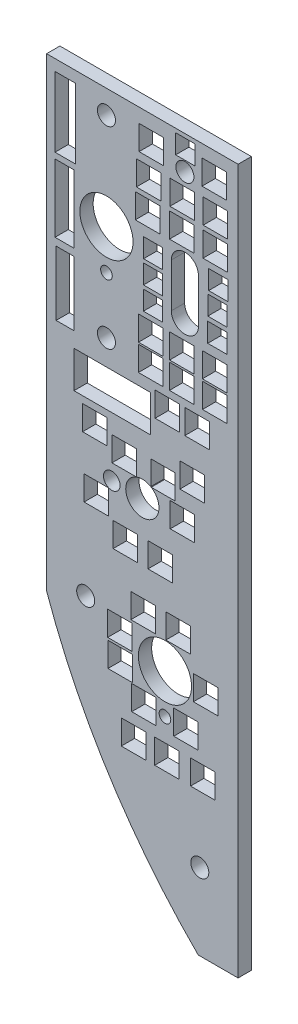
SolidWorks part; units mm, degrees
material "Acrylic (Medium-high impact)"
ref_plane "Front Plane" through (0, 0, 0) normal (0, 0, 1) x (1, 0, 0)
ref_plane "Top Plane" through (0, 0, 0) normal (0, 1, 0) x (1, 0, 0)
ref_plane "Right Plane" through (0, 0, 0) normal (1, 0, 0) x (0, 0, -1)
sketch "Sketch1" plane through (0, 0, 0) normal (0, 0, 1) x (1, 0, 0)
  line L4 (-45.72, 26.9875) -> (-45.72, -84.1375)
  line L5 (-9.525, -141.2875) -> (0, -141.2875)
  line L6 (0, -141.2875) -> (0, 26.9875)
  line L7 (0, 26.9875) -> (-45.72, 26.9875)
  line L8 (-45.72, 26.9875) -> (-45.72, -84.1375)
  line L9 (-9.525, -141.2875) -> (0, -141.2875)
  line L10 (0, -141.2875) -> (0, 26.9875)
  line L11 (0, 26.9875) -> (-45.72, 26.9875)
  arc A1 (-45.72, -84.1375) -> (-9.525, -141.2875) centre (97.9169, -33.2042) ccw
  arc A2 (-45.72, -84.1375) -> (-9.525, -141.2875) centre (97.9169, -33.2042) ccw
  dimension "D1" = 0
extrude "Boss-Extrude1" add sketch "Sketch1" against normal blind 3.175
hole_wizard "1/2 (0.5) Diameter Hole1" positions "Sketch4" profile "Sketch3" hole size "1/2" standard "ANSI Inch" end condition through all
sketch "Sketch4" plane through (0, 0, 0) normal (0, 0, 1) x (1, 0, 0)
  point P0 (-17.4625, -86.5505)
  point P4 (-31.4325, -1.6203)
sketch "Sketch3" plane through (-17.4625, -86.5505, 0) normal (1, 0, 0) x (0, -1, 0)
  line L0 (0, 0) -> (0, 3.175)
  line L1 (0, 3.175) -> (6.35, 3.175)
  line L2 (6.35, 3.175) -> (6.35, 0)
  line L5 (6.35, 0) -> (0, 0)
  line L11 (0, -6.35) -> (0, 107.95) construction
  dimension "Thru Hole Dia." = 12.7
  dimension "Thru Hole Depth" = 3.175
hole_wizard "5/16 (0.3125) Diameter Hole1" positions "Sketch6" profile "Sketch5" hole size "5/16" standard "ANSI Inch" end condition through all
sketch "Sketch6" plane through (0, 0, 0) normal (0, 0, 1) x (1, 0, 0)
  point P0 (-22.86, -53.5305)
sketch "Sketch5" plane through (-22.86, -53.5305, 0) normal (1, 0, 0) x (0, -1, 0)
  line L0 (0, 0) -> (0, 3.175)
  line L1 (0, 3.175) -> (3.9687, 3.175)
  line L2 (3.9687, 3.175) -> (3.9687, 0)
  line L5 (3.9687, 0) -> (0, 0)
  line L11 (0, -6.35) -> (0, 107.95) construction
  dimension "Thru Hole Dia." = 7.9375
  dimension "Thru Hole Depth" = 3.175
hole_wizard "5/32 (0.15625) Diameter Hole1" positions "Sketch8" profile "Sketch7" hole size "5/32" standard "ANSI Inch" end condition through all
sketch "Sketch8" plane through (0, 0, 0) normal (0, 0, 1) x (1, 0, 0)
  line L0 (-22.86, -49.5617) -> (-22.86, -53.5305) construction
  circle A0 centre (-22.86, -53.5305) radius 3.9688 construction
  point P11 (-30.1611, -53.5305)
sketch "Sketch7" plane through (-30.1611, -53.5305, 0) normal (1, 0, 0) x (0, -1, 0)
  line L0 (0, 0) -> (0, 3.175)
  line L1 (0, 3.175) -> (1.9844, 3.175)
  line L2 (1.9844, 3.175) -> (1.9844, 0)
  line L5 (1.9844, 0) -> (0, 0)
  line L11 (0, -6.35) -> (0, 107.95) construction
  dimension "Thru Hole Dia." = 3.9688
  dimension "Thru Hole Depth" = 3.175
hole_wizard "7/64 (0.10938) Diameter Hole1" positions "Sketch10" profile "Sketch9" hole size "7/64" standard "ANSI Inch" end condition through all
sketch "Sketch10" plane through (0, 0, 0) normal (0, 0, 1) x (1, 0, 0)
  point P0 (-17.4646, -95.9667)
  point P3 (-31.4325, -11.1589)
sketch "Sketch9" plane through (-17.4646, -95.9667, 0) normal (1, 0, 0) x (0, -1, 0)
  line L0 (0, 0) -> (0, 3.175)
  line L1 (0, 3.175) -> (1.3891, 3.175)
  line L2 (1.3891, 3.175) -> (1.3891, 0)
  line L5 (1.3891, 0) -> (0, 0)
  line L11 (0, -6.35) -> (0, 107.95) construction
  dimension "Thru Hole Dia." = 2.7783
  dimension "Thru Hole Depth" = 3.175
sketch "Sketch11" plane through (0, 0, -3.175) normal (0, 0, -1) x (-1, 0, 0)
  line L5 (19.8437, -15.24) -> (19.8437, 3.175)
  line L6 (19.8437, 3.175) -> (8.7312, 3.175)
  line L7 (8.7312, 3.175) -> (8.7312, -15.24)
  line L8 (8.7312, -15.24) -> (19.8437, -15.24)
  line L9 (19.8437, -15.24) -> (19.8437, 3.175)
  line L10 (19.8437, 3.175) -> (8.7312, 3.175)
  line L11 (8.7312, 3.175) -> (8.7312, -15.24)
  line L12 (8.7312, -15.24) -> (19.8437, -15.24)
  dimension "D1" = 0
extrude "Cut-Extrude4" [suppressed] cut sketch "Sketch11" against normal through all
hole_wizard "#6 Clearance Hole1" positions "Sketch13" profile "Sketch12" hole size "#6" standard "ANSI Inch" end condition through all
sketch "Sketch13" plane through (0, 0, -3.175) normal (0, 0, -1) x (-1, 0, 0)
  point P0 (12.7, 19.05)
  point P3 (36.3855, -80.4545)
  point P6 (9.144, -122.9995)
  point P10 (31.4325, -24.62)
  point P13 (31.4325, 21.4048)
sketch "Sketch12" plane through (-12.7, 19.05, -3.175) normal (1, 0, 0) x (0, 1, 0)
  line L0 (0, 0) -> (0, 3.175)
  line L1 (0, 3.175) -> (2.1526, 3.175)
  line L2 (2.1526, 3.175) -> (2.1526, 0)
  line L5 (2.1526, 0) -> (0, 0)
  line L11 (0, -6.35) -> (0, 107.95) construction
  dimension "Thru Hole Dia." = 4.3053
  dimension "Thru Hole Depth" = 3.175
hole_wizard "#16 (0.177) Diameter Hole1" positions "Sketch15" profile "Sketch14" hole size "#16" standard "ANSI Inch" end condition through all
sketch "Sketch15" plane through (0, 0, -3.175) normal (0, 0, -1) x (-1, 0, 0)
  line L5 (12.7, 2.794) -> (12.7, -14.859) construction
  line L6 (12.7, -6.0325) -> (17.8753, -6.0325) construction
  point P26 (12.7, -0.7804)
  point P33 (12.7, -11.2846)
sketch "Sketch14" plane through (-12.7, -11.2846, -3.175) normal (1, 0, 0) x (0, 1, 0)
  line L0 (0, 0) -> (0, 3.175)
  line L1 (0, 3.175) -> (2.2479, 3.175)
  line L2 (2.2479, 3.175) -> (2.2479, 0)
  line L5 (2.2479, 0) -> (0, 0)
  line L11 (0, -6.35) -> (0, 107.95) construction
  dimension "Thru Hole Dia." = 4.4958
  dimension "Thru Hole Depth" = 3.175
sketch "Sketch16" plane through (0, 0, -4.775) normal (0, 0, -1) x (-1, 0, 0)
  line L0 (12.7, -11.2846) -> (12.7, -0.7804) construction
  line L1 (2.6659, -22.1354) -> (8.5079, -22.1354)
  line L2 (2.6659, -22.1354) -> (2.6659, -27.9774)
  line L3 (2.6659, -27.9774) -> (8.5079, -27.9774)
  line L4 (8.5079, -22.1354) -> (8.5079, -27.9774)
  line L5 (2.6659, -22.1354) -> (8.5079, -27.9774) construction
  line L6 (2.6659, -27.9774) -> (8.5079, -22.1354) construction
  line L7 (10.5519, -22.1354) -> (16.3939, -22.1354)
  line L8 (10.5519, -22.1354) -> (10.5519, -27.9774)
  line L9 (10.5519, -27.9774) -> (16.3939, -27.9774)
  line L10 (16.3939, -22.1354) -> (16.3939, -27.9774)
  line L11 (10.5519, -22.1354) -> (16.3939, -27.9774) construction
  line L12 (10.5519, -27.9774) -> (16.3939, -22.1354) construction
  line L13 (17.9569, -22.1354) -> (23.7989, -22.1354)
  line L14 (17.9569, -22.1354) -> (17.9569, -27.9774)
  line L15 (17.9569, -27.9774) -> (23.7989, -27.9774)
  line L16 (23.7989, -22.1354) -> (23.7989, -27.9774)
  line L17 (17.9569, -22.1354) -> (23.7989, -27.9774) construction
  line L18 (17.9569, -27.9774) -> (23.7989, -22.1354) construction
  line L19 (17.9319, -15.8614) -> (23.7739, -15.8614)
  line L20 (17.9319, -15.8614) -> (17.9319, -21.7034)
  line L21 (17.9319, -21.7034) -> (23.7739, -21.7034)
  line L22 (23.7739, -15.8614) -> (23.7739, -21.7034)
  line L23 (17.9319, -15.8614) -> (23.7739, -21.7034) construction
  line L24 (17.9319, -21.7034) -> (23.7739, -15.8614) construction
  line L25 (10.5149, -15.8364) -> (16.3569, -15.8364)
  line L26 (10.5149, -15.8364) -> (10.5149, -21.6784)
  line L27 (10.5149, -21.6784) -> (16.3569, -21.6784)
  line L28 (16.3569, -15.8364) -> (16.3569, -21.6784)
  line L29 (10.5149, -15.8364) -> (16.3569, -21.6784) construction
  line L30 (10.5149, -21.6784) -> (16.3569, -15.8364) construction
  line L31 (2.6919, -15.8114) -> (8.5339, -15.8114)
  line L32 (2.6919, -15.8114) -> (2.6919, -21.6534)
  line L33 (2.6919, -21.6534) -> (8.5339, -21.6534)
  line L34 (8.5339, -15.8114) -> (8.5339, -21.6534)
  line L35 (2.6919, -15.8114) -> (8.5339, -21.6534) construction
  line L36 (2.6919, -21.6534) -> (8.5339, -15.8114) construction
  line L41 (39.2165, -27.0307) -> (43.4505, -27.0307)
  line L42 (39.2165, -27.0307) -> (39.2165, -11.6644)
  line L47 (39.2165, -11.6644) -> (43.4505, -11.6644)
  line L48 (43.4505, -27.0307) -> (43.4505, -11.6644)
  line L53 (39.2165, 6.231) -> (43.7187, 6.231)
  line L54 (39.2165, 6.231) -> (39.2165, -9.9754)
  line L55 (39.2165, -9.9754) -> (43.7187, -9.9754)
  line L56 (43.7187, 6.231) -> (43.7187, -9.9754)
  line L57 (38.8582, 7.6135) -> (43.7187, 7.6135)
  line L58 (38.8582, 7.6135) -> (38.8582, 24.3196)
  line L59 (38.8582, 24.3196) -> (43.7187, 24.3196)
  line L60 (43.7187, 7.6135) -> (43.7187, 24.3196)
  line L61 (12.7249, -29.6544) -> (6.8829, -29.6544)
  line L62 (12.7249, -29.6544) -> (12.7249, -35.4964)
  line L63 (12.7249, -35.4964) -> (6.8829, -35.4964)
  line L64 (6.8829, -29.6544) -> (6.8829, -35.4964)
  line L65 (12.7249, -29.6544) -> (6.8829, -35.4964) construction
  line L66 (12.7249, -35.4964) -> (6.8829, -29.6544) construction
  line L67 (19.8109, -29.6034) -> (13.9689, -29.6034)
  line L68 (19.8109, -29.6034) -> (19.8109, -35.4454)
  line L69 (19.8109, -35.4454) -> (13.9689, -35.4454)
  line L70 (13.9689, -29.6034) -> (13.9689, -35.4454)
  line L71 (19.8109, -29.6034) -> (13.9689, -35.4454) construction
  line L72 (19.8109, -35.4454) -> (13.9689, -29.6034) construction
  line L73 (5.5089, -101.4346) -> (11.3509, -101.4346)
  line L74 (5.5089, -101.4346) -> (5.5089, -107.2766)
  line L75 (5.5089, -107.2766) -> (11.3509, -107.2766)
  line L76 (11.3509, -101.4346) -> (11.3509, -107.2766)
  line L77 (5.5089, -101.4346) -> (11.3509, -107.2766) construction
  line L78 (5.5089, -107.2766) -> (11.3509, -101.4346) construction
  line L79 (14.0689, -101.4088) -> (19.9109, -101.4088)
  line L80 (14.0689, -101.4088) -> (14.0689, -107.2508)
  line L81 (14.0689, -107.2508) -> (19.9109, -107.2508)
  line L82 (19.9109, -101.4088) -> (19.9109, -107.2508)
  line L83 (14.0689, -101.4088) -> (19.9109, -107.2508) construction
  line L84 (14.0689, -107.2508) -> (19.9109, -101.4088) construction
  line L85 (22.0469, -101.4342) -> (27.8889, -101.4342)
  line L86 (22.0469, -101.4342) -> (22.0469, -107.2762)
  line L87 (22.0469, -107.2762) -> (27.8889, -107.2762)
  line L88 (27.8889, -101.4342) -> (27.8889, -107.2762)
  line L89 (22.0469, -101.4342) -> (27.8889, -107.2762) construction
  line L90 (22.0469, -107.2762) -> (27.8889, -101.4342) construction
  line L91 (9.5239, -93.1288) -> (15.3659, -93.1288)
  line L92 (9.5239, -93.1288) -> (9.5239, -98.9708)
  line L93 (9.5239, -98.9708) -> (15.3659, -98.9708)
  line L94 (15.3659, -93.1288) -> (15.3659, -98.9708)
  line L95 (9.5239, -93.1288) -> (15.3659, -98.9708) construction
  line L96 (9.5239, -98.9708) -> (15.3659, -93.1288) construction
  line L97 (19.5569, -93.0776) -> (25.3989, -93.0776)
  line L98 (19.5569, -93.0776) -> (19.5569, -98.9196)
  line L99 (19.5569, -98.9196) -> (25.3989, -98.9196)
  line L100 (25.3989, -93.0776) -> (25.3989, -98.9196)
  line L101 (19.5569, -93.0776) -> (25.3989, -98.9196) construction
  line L102 (19.5569, -98.9196) -> (25.3989, -93.0776) construction
  line L103 (4.8249, -83.6546) -> (10.6669, -83.6546)
  line L104 (4.8249, -83.6546) -> (4.8249, -89.4966)
  line L105 (4.8249, -89.4966) -> (10.6669, -89.4966)
  line L106 (10.6669, -83.6546) -> (10.6669, -89.4966)
  line L107 (4.8249, -83.6546) -> (10.6669, -89.4966) construction
  line L108 (4.8249, -89.4966) -> (10.6669, -83.6546) construction
  line L109 (25.2329, -86.9818) -> (31.0749, -86.9818)
  line L110 (25.2329, -86.9818) -> (25.2329, -92.8238)
  line L111 (25.2329, -92.8238) -> (31.0749, -92.8238)
  line L112 (31.0749, -86.9818) -> (31.0749, -92.8238)
  line L113 (25.2329, -86.9818) -> (31.0749, -92.8238) construction
  line L114 (25.2329, -92.8238) -> (31.0749, -86.9818) construction
  line L115 (25.2959, -80.5808) -> (31.1379, -80.5808)
  line L116 (25.2959, -80.5808) -> (25.2959, -86.4228)
  line L117 (25.2959, -86.4228) -> (31.1379, -86.4228)
  line L118 (31.1379, -80.5808) -> (31.1379, -86.4228)
  line L119 (25.2959, -80.5808) -> (31.1379, -86.4228) construction
  line L120 (25.2959, -86.4228) -> (31.1379, -80.5808) construction
  line L121 (19.7609, -74.1546) -> (25.6029, -74.1546)
  line L122 (19.7609, -74.1546) -> (19.7609, -79.9966)
  line L123 (19.7609, -79.9966) -> (25.6029, -79.9966)
  line L124 (25.6029, -74.1546) -> (25.6029, -79.9966)
  line L125 (19.7609, -74.1546) -> (25.6029, -79.9966) construction
  line L126 (19.7609, -79.9966) -> (25.6029, -74.1546) construction
  line L127 (11.4019, -74.1804) -> (17.2439, -74.1804)
  line L128 (11.4019, -74.1804) -> (11.4019, -80.0224)
  line L129 (11.4019, -80.0224) -> (17.2439, -80.0224)
  line L130 (17.2439, -74.1804) -> (17.2439, -80.0224)
  line L131 (11.4019, -74.1804) -> (17.2439, -80.0224) construction
  line L132 (11.4019, -80.0224) -> (17.2439, -74.1804) construction
  line L133 (15.6709, -61.6074) -> (21.5129, -61.6074)
  line L134 (15.6709, -61.6074) -> (15.6709, -67.4494)
  line L135 (15.6709, -67.4494) -> (21.5129, -67.4494)
  line L136 (21.5129, -61.6074) -> (21.5129, -67.4494)
  line L137 (15.6709, -61.6074) -> (21.5129, -67.4494) construction
  line L138 (15.6709, -67.4494) -> (21.5129, -61.6074) construction
  line L139 (24.0019, -61.582) -> (29.8439, -61.582)
  line L140 (24.0019, -61.582) -> (24.0019, -67.424)
  line L141 (24.0019, -67.424) -> (29.8439, -67.424)
  line L142 (29.8439, -61.582) -> (29.8439, -67.424)
  line L143 (24.0019, -61.582) -> (29.8439, -67.424) construction
  line L144 (24.0019, -67.424) -> (29.8439, -61.582) construction
  line L145 (30.9369, -55.4098) -> (36.7789, -55.4098)
  line L146 (30.9369, -55.4098) -> (30.9369, -61.2518)
  line L147 (30.9369, -61.2518) -> (36.7789, -61.2518)
  line L148 (36.7789, -55.4098) -> (36.7789, -61.2518)
  line L149 (30.9369, -55.4098) -> (36.7789, -61.2518) construction
  line L150 (30.9369, -61.2518) -> (36.7789, -55.4098) construction
  line L151 (10.3599, -50.66) -> (16.2019, -50.66)
  line L152 (10.3599, -50.66) -> (10.3599, -56.502)
  line L153 (10.3599, -56.502) -> (16.2019, -56.502)
  line L154 (16.2019, -50.66) -> (16.2019, -56.502)
  line L155 (10.3599, -50.66) -> (16.2019, -56.502) construction
  line L156 (10.3599, -56.502) -> (16.2019, -50.66) construction
  line L157 (8.0509, -41.2874) -> (13.8929, -41.2874)
  line L158 (8.0509, -41.2874) -> (8.0509, -47.1294)
  line L159 (8.0509, -47.1294) -> (13.8929, -47.1294)
  line L160 (13.8929, -41.2874) -> (13.8929, -47.1294)
  line L161 (8.0509, -41.2874) -> (13.8929, -47.1294) construction
  line L162 (8.0509, -47.1294) -> (13.8929, -41.2874) construction
  line L163 (15.0109, -44.3354) -> (20.8529, -44.3354)
  line L164 (15.0109, -44.3354) -> (15.0109, -50.1774)
  line L165 (15.0109, -50.1774) -> (20.8529, -50.1774)
  line L166 (20.8529, -44.3354) -> (20.8529, -50.1774)
  line L167 (15.0109, -44.3354) -> (20.8529, -50.1774) construction
  line L168 (15.0109, -50.1774) -> (20.8529, -44.3354) construction
  line L169 (24.2819, -43.9798) -> (30.1239, -43.9798)
  line L170 (24.2819, -43.9798) -> (24.2819, -49.8218)
  line L171 (24.2819, -49.8218) -> (30.1239, -49.8218)
  line L172 (30.1239, -43.9798) -> (30.1239, -49.8218)
  line L173 (24.2819, -43.9798) -> (30.1239, -49.8218) construction
  line L174 (24.2819, -49.8218) -> (30.1239, -43.9798) construction
  line L175 (31.2919, -41.0588) -> (37.1339, -41.0588)
  line L176 (31.2919, -41.0588) -> (31.2919, -46.9008)
  line L177 (31.2919, -46.9008) -> (37.1339, -46.9008)
  line L178 (37.1339, -41.0588) -> (37.1339, -46.9008)
  line L179 (31.2919, -41.0588) -> (37.1339, -46.9008) construction
  line L180 (31.2919, -46.9008) -> (37.1339, -41.0588) construction
  line L185 (9.4609, -11.2846) -> (9.4609, -0.7804)
  line L186 (15.9391, -11.2846) -> (15.9391, -0.7804)
  line L191 (39.1895, -30.6633) -> (20.8742, -30.6633)
  line L192 (39.1895, -30.6633) -> (39.1895, -39.4353)
  line L193 (2.6809, -9.0944) -> (7.2529, -9.0944)
  line L194 (2.6809, -9.0944) -> (2.6809, -13.6664)
  line L195 (2.6809, -13.6664) -> (7.2529, -13.6664)
  line L196 (7.2529, -9.0944) -> (7.2529, -13.6664)
  line L197 (2.6809, -9.0944) -> (7.2529, -13.6664) construction
  line L198 (2.6809, -13.6664) -> (7.2529, -9.0944) construction
  line L199 (2.6659, -3.4664) -> (7.2379, -3.4664)
  line L200 (2.6659, -3.4664) -> (2.6659, -8.0384)
  line L201 (2.6659, -8.0384) -> (7.2379, -8.0384)
  line L202 (7.2379, -3.4664) -> (7.2379, -8.0384)
  line L203 (2.6659, -3.4664) -> (7.2379, -8.0384) construction
  line L204 (2.6659, -8.0384) -> (7.2379, -3.4664) construction
  line L205 (2.4609, 1.9176) -> (7.0329, 1.9176)
  line L206 (2.4609, 1.9176) -> (2.4609, -2.6544)
  line L207 (2.4609, -2.6544) -> (7.0329, -2.6544)
  line L208 (7.0329, 1.9176) -> (7.0329, -2.6544)
  line L209 (2.4609, 1.9176) -> (7.0329, -2.6544) construction
  line L210 (2.4609, -2.6544) -> (7.0329, 1.9176) construction
  line L211 (2.5389, 9.2076) -> (8.3809, 9.2076)
  line L212 (2.5389, 9.2076) -> (2.5389, 3.3656)
  line L213 (2.5389, 3.3656) -> (8.3809, 3.3656)
  line L214 (8.3809, 9.2076) -> (8.3809, 3.3656)
  line L215 (2.5389, 9.2076) -> (8.3809, 3.3656) construction
  line L216 (2.5389, 3.3656) -> (8.3809, 9.2076) construction
  line L217 (10.5379, 9.1566) -> (16.3799, 9.1566)
  line L218 (10.5379, 9.1566) -> (10.5379, 3.3146)
  line L219 (10.5379, 3.3146) -> (16.3799, 3.3146)
  line L220 (16.3799, 9.1566) -> (16.3799, 3.3146)
  line L221 (10.5379, 9.1566) -> (16.3799, 3.3146) construction
  line L222 (10.5379, 3.3146) -> (16.3799, 9.1566) construction
  line L223 (18.7049, 9.0556) -> (24.5469, 9.0556)
  line L224 (18.7049, 9.0556) -> (18.7049, 3.2136)
  line L225 (18.7049, 3.2136) -> (24.5469, 3.2136)
  line L226 (24.5469, 9.0556) -> (24.5469, 3.2136)
  line L227 (18.7049, 9.0556) -> (24.5469, 3.2136) construction
  line L228 (18.7049, 3.2136) -> (24.5469, 9.0556) construction
  line L229 (17.9969, 0.7356) -> (22.5689, 0.7356)
  line L230 (17.9969, 0.7356) -> (17.9969, -3.8364)
  line L231 (17.9969, -3.8364) -> (22.5689, -3.8364)
  line L232 (22.5689, 0.7356) -> (22.5689, -3.8364)
  line L233 (17.9969, 0.7356) -> (22.5689, -3.8364) construction
  line L234 (17.9969, -3.8364) -> (22.5689, 0.7356) construction
  line L235 (18.0219, -4.6994) -> (22.5939, -4.6994)
  line L236 (18.0219, -4.6994) -> (18.0219, -9.2714)
  line L237 (18.0219, -9.2714) -> (22.5939, -9.2714)
  line L238 (22.5939, -4.6994) -> (22.5939, -9.2714)
  line L239 (18.0219, -4.6994) -> (22.5939, -9.2714) construction
  line L240 (18.0219, -9.2714) -> (22.5939, -4.6994) construction
  line L241 (18.0479, -10.1354) -> (22.6199, -10.1354)
  line L242 (18.0479, -10.1354) -> (18.0479, -14.7074)
  line L243 (18.0479, -14.7074) -> (22.6199, -14.7074)
  line L244 (22.6199, -10.1354) -> (22.6199, -14.7074)
  line L245 (18.0479, -10.1354) -> (22.6199, -14.7074) construction
  line L246 (18.0479, -14.7074) -> (22.6199, -10.1354) construction
  line L247 (2.4859, 16.0666) -> (8.3279, 16.0666)
  line L248 (2.4859, 16.0666) -> (2.4859, 10.2246)
  line L249 (2.4859, 10.2246) -> (8.3279, 10.2246)
  line L250 (8.3279, 16.0666) -> (8.3279, 10.2246)
  line L251 (2.4859, 16.0666) -> (8.3279, 10.2246) construction
  line L252 (2.4859, 10.2246) -> (8.3279, 16.0666) construction
  line L253 (10.4389, 15.9896) -> (16.2809, 15.9896)
  line L254 (10.4389, 15.9896) -> (10.4389, 10.1476)
  line L255 (10.4389, 10.1476) -> (16.2809, 10.1476)
  line L256 (16.2809, 15.9896) -> (16.2809, 10.1476)
  line L257 (10.4389, 15.9896) -> (16.2809, 10.1476) construction
  line L258 (10.4389, 10.1476) -> (16.2809, 15.9896) construction
  line L259 (18.4399, 15.9896) -> (24.2819, 15.9896)
  line L260 (18.4399, 15.9896) -> (18.4399, 10.1476)
  line L261 (18.4399, 10.1476) -> (24.2819, 10.1476)
  line L262 (24.2819, 15.9896) -> (24.2819, 10.1476)
  line L263 (18.4399, 15.9896) -> (24.2819, 10.1476) construction
  line L264 (18.4399, 10.1476) -> (24.2819, 15.9896) construction
  line L265 (17.8049, 23.6096) -> (23.6469, 23.6096)
  line L266 (17.8049, 23.6096) -> (17.8049, 17.7676)
  line L267 (17.8049, 17.7676) -> (23.6469, 17.7676)
  line L268 (23.6469, 23.6096) -> (23.6469, 17.7676)
  line L269 (17.8049, 23.6096) -> (23.6469, 17.7676) construction
  line L270 (17.8049, 17.7676) -> (23.6469, 23.6096) construction
  line L271 (2.7659, 23.9906) -> (8.6079, 23.9906)
  line L272 (2.7659, 23.9906) -> (2.7659, 18.1486)
  line L273 (2.7659, 18.1486) -> (8.6079, 18.1486)
  line L274 (8.6079, 23.9906) -> (8.6079, 18.1486)
  line L275 (2.7659, 23.9906) -> (8.6079, 18.1486) construction
  line L276 (2.7659, 18.1486) -> (8.6079, 23.9906) construction
  line L277 (10.3369, 26.0476) -> (14.9089, 26.0476)
  line L278 (10.3369, 26.0476) -> (10.3369, 21.4756)
  line L279 (10.3369, 21.4756) -> (14.9089, 21.4756)
  line L280 (14.9089, 26.0476) -> (14.9089, 21.4756)
  line L281 (10.3369, 26.0476) -> (14.9089, 21.4756) construction
  line L282 (10.3369, 21.4756) -> (14.9089, 26.0476) construction
  line L283 (39.1895, -39.4353) -> (20.8742, -39.4353)
  line L284 (20.8742, -30.6633) -> (20.8742, -39.4353)
  arc A0 (9.4609, -11.2846) -> (15.9391, -11.2846) centre (12.7, -11.2846) ccw
  arc A1 (15.9391, -0.7804) -> (9.4609, -0.7804) centre (12.7, -0.7804) ccw
  point P0 (5.5869, -25.0564)
  point P6 (13.4729, -25.0564)
  point P12 (20.8779, -25.0564)
  point P18 (20.8529, -18.7824)
  point P24 (13.4359, -18.7574)
  point P30 (5.6129, -18.7324)
  point P50 (9.8039, -32.5754)
  point P57 (16.8899, -32.5244)
  point P63 (8.4299, -104.3556)
  point P75 (24.9679, -104.3552)
  point P81 (12.4449, -96.0498)
  point P87 (22.4779, -95.9986)
  point P93 (7.7459, -86.5756)
  point P99 (28.1539, -89.9028)
  point P105 (28.2169, -83.5018)
  point P111 (22.6819, -77.0756)
  point P117 (14.3229, -77.1014)
  point P123 (18.5919, -64.5284)
  point P129 (26.9229, -64.503)
  point P135 (33.8579, -58.3308)
  point P141 (13.2809, -53.581)
  point P147 (10.9719, -44.2084)
  point P153 (17.9319, -47.2564)
  point P159 (27.2029, -46.9008)
  point P165 (34.2129, -43.9798)
  point P173 (12.7, -6.0325)
  point P183 (4.9669, -11.3804)
  point P189 (4.9519, -5.7524)
  point P195 (4.7469, -0.3684)
  point P201 (5.4599, 6.2866)
  point P207 (13.4589, 6.2356)
  point P213 (21.6259, 6.1346)
  point P219 (20.2829, -1.5504)
  point P225 (20.3079, -6.9854)
  point P231 (20.3339, -12.4214)
  point P237 (5.4069, 13.1456)
  point P243 (13.3599, 13.0686)
  point P249 (21.3609, 13.0686)
  point P255 (20.7259, 20.6886)
  point P261 (5.6869, 21.0696)
  point P267 (12.6229, 23.7616)
  dimension "D1" = 5.842
  dimension "D2" = 5.842
  dimension "D3" = 4.572
extrude "Cut-Extrude5" cut sketch "Sketch16" against normal through all
